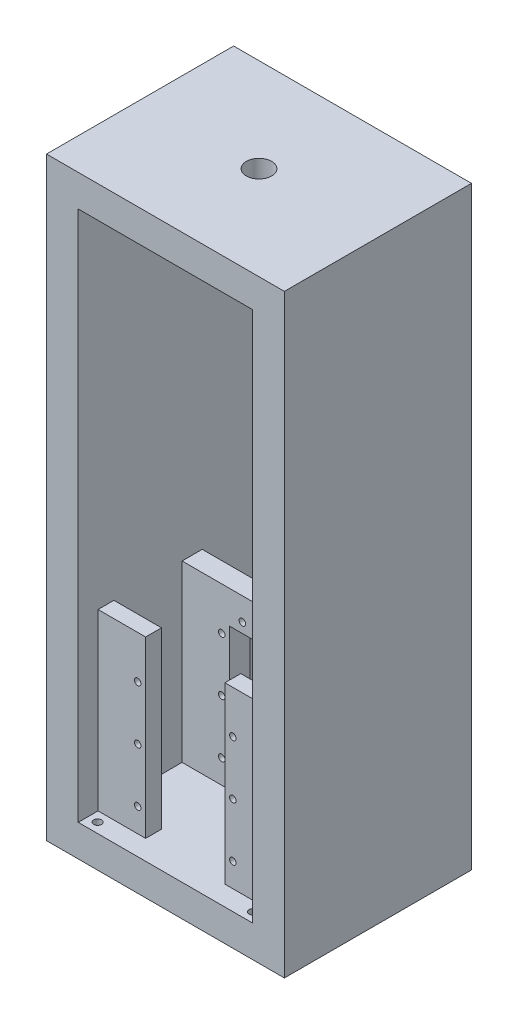
SolidWorks part; units mm, degrees
ref_plane "Front Plane" through (0, 0, 0) normal (0, 0, 1) x (1, 0, 0)
ref_plane "Top Plane" through (0, 0, 0) normal (0, 1, 0) x (1, 0, 0)
ref_plane "Right Plane" through (0, 0, 0) normal (1, 0, 0) x (0, 0, -1)
sketch "Sketch1" plane through (0, 0, 0) normal (0, 0, 1) x (1, 0, 0)
  line L1 (0, 0) -> (75, 0)
  line L2 (0, 0) -> (0, 187.5)
  line L3 (0, 187.5) -> (75, 187.5)
  line L4 (75, 0) -> (75, 187.5)
  line L5 (10, 10) -> (65, 10)
  line L6 (10, 10) -> (10, 177.5)
  line L7 (10, 177.5) -> (65, 177.5)
  line L8 (65, 10) -> (65, 177.5)
  dimension "D1" = 75
  dimension "D2" = 187.5
  dimension "D3" = 10
  dimension "D4" = 10
  dimension "D5" = 10
  dimension "D6" = 10
extrude "Boss-Extrude1" add sketch "Sketch1" against normal blind 59
ref_plane "Plane1" through (0, 0, -37.5) normal (0, 0, 1) x (1, 0, 0)
hole_wizard "Tap Drill for M5x0.8 Tap2" positions "Sketch8" profile "Sketch9" hole size "M5x0.8" standard "ANSI Metric" end condition through all
sketch "Sketch8" plane through (0, 10, 0) normal (0, 1, 0) x (1, 0, 0)
  line L0 (37.5, 59) -> (37.5, 0) construction
  line L1 (10, 59) -> (65, 59) construction
  line L2 (10, 0) -> (65, 0) construction
  point P0 (37.5, 29.5)
sketch "Sketch9" plane through (37.5, 10, -29.5) normal (1, 0, 0) x (0, 0, 1)
  line L0 (0, 0) -> (0, 10)
  line L1 (0, 10) -> (2.1, 10)
  line L2 (2.1, 10) -> (2.1, 0)
  line L5 (2.1, 0) -> (0, 0)
  line L11 (0, -6.35) -> (0, 107.95) construction
  dimension "Thru Hole Dia." = 4.2
  dimension "Thru Hole Depth" = 10
sketch "Sketch13" plane through (0, 10, 0) normal (0, 1, 0) x (1, 0, 0)
  line L0 (65, 59) -> (65, 0) construction
  line L1 (65, 32.75) -> (50, 32.75)
  line L2 (65, 32.75) -> (65, 39.1)
  line L3 (65, 39.1) -> (50, 39.1)
  line L4 (50, 32.75) -> (50, 39.1)
  line L5 (37.5, 59) -> (37.5, 0) construction
  line L6 (10, 59) -> (65, 59) construction
  line L7 (10, 0) -> (65, 0) construction
  line L8 (10, 39.1) -> (25, 39.1)
  line L9 (25, 32.75) -> (25, 39.1)
  line L10 (10, 32.75) -> (25, 32.75)
  line L11 (10, 32.75) -> (10, 39.1)
  line L12 (10, 11.25) -> (25, 11.25)
  line L13 (65, 6.25) -> (50, 6.25)
  line L14 (65, 6.25) -> (65, 11.25)
  line L15 (65, 11.25) -> (50, 11.25)
  line L16 (50, 6.25) -> (50, 11.25)
  line L17 (25, 6.25) -> (25, 11.25)
  line L18 (10, 6.25) -> (25, 6.25)
  line L19 (10, 6.25) -> (10, 11.25)
  dimension "D1" = 26.25
  dimension "D2" = 12.5
  dimension "D3" = 6.35
  dimension "D4" = 6.25
  dimension "D5" = 5
  dimension "D6" = 15
extrude "Boss-Extrude2" add sketch "Sketch13" along normal blind 55
sketch "Sketch14" plane through (50, 0, 0) normal (-1, 0, 0) x (0, 0, 1)
  line L0 (-32.75, 65) -> (-32.75, 10) construction
  line L1 (-39.1, 65) -> (-32.75, 65)
  line L2 (-39.1, 65) -> (-39.1, 54.7)
  line L3 (-39.1, 54.7) -> (-32.75, 54.7)
  line L4 (-32.75, 65) -> (-32.75, 54.7)
  dimension "D1" = 10.3
extrude "Boss-Extrude3" add sketch "Sketch14" along normal up to surface (25 mm away) contours L1 L4 L3 L2 up to face at (25, 37.5, -35.925)
sketch "Sketch17" plane through (0, 0, -39.1) normal (0, 0, -1) x (-1, 0, 0)
  line L0 (-37.5, 65) -> (-37.5, 10) construction
  line L1 (-65, 65) -> (-10, 65) construction
  line L2 (-10, 10) -> (-65, 10) construction
  line L3 (-22.5, 65) -> (-22.5, 10) construction
  line L5 (-25, 10) -> (-10, 10) construction
  line L6 (-29, 65) -> (-29, 10) construction
  line L8 (-65, 17.5) -> (-10, 17.5) construction
  line L9 (-65, 10) -> (-65, 177.5) construction
  line L10 (-10, 65) -> (-10, 10) construction
  line L11 (-65, 34.5) -> (-10, 34.5) construction
  line L12 (-65, 51.5) -> (-10, 51.5) construction
  line L13 (-65, 57.8) -> (-10, 57.8) construction
  line L14 (-52.5, 65) -> (-52.5, 10) construction
  line L15 (-46, 65) -> (-46, 10) construction
  dimension "D1" = 15
  dimension "D2" = 6.5
  dimension "D3" = 7.5
  dimension "D4" = 17
  dimension "D5" = 17
  dimension "D6" = 6.3
hole_wizard "Tap Drill for M2.5x0.45 Tap1" positions "Sketch18" profile "Sketch19" hole size "M2.5x0.45" standard "ANSI Metric" end condition through all
sketch "Sketch18" plane through (0, 0, -39.1) normal (0, 0, -1) x (-1, 0, 0)
  line L0 (-65, 57.8) -> (-10, 57.8) construction
  line L1 (-46, 65) -> (-46, 10) construction
  line L2 (-29, 65) -> (-29, 10) construction
  line L3 (-22.5, 65) -> (-22.5, 10) construction
  line L4 (-65, 51.5) -> (-10, 51.5) construction
  line L5 (-52.5, 65) -> (-52.5, 10) construction
  line L6 (-65, 34.5) -> (-10, 34.5) construction
  line L7 (-65, 17.5) -> (-10, 17.5) construction
  point P0 (-46, 57.8)
  point P2 (-52.5, 51.5)
  point P4 (-52.5, 34.5)
  point P6 (-52.5, 17.5)
  point P8 (-22.5, 17.5)
  point P10 (-22.5, 34.5)
  point P12 (-22.5, 51.5)
  point P14 (-29, 57.8)
sketch "Sketch19" plane through (46, 57.8, -39.1) normal (1, 0, 0) x (0, 1, 0)
  line L0 (0, 0) -> (0, 39.1)
  line L1 (0, 39.1) -> (1.025, 39.1)
  line L2 (1.025, 39.1) -> (1.025, 0)
  line L5 (1.025, 0) -> (0, 0)
  line L11 (0, -6.35) -> (0, 107.95) construction
  dimension "Thru Hole Dia." = 2.05
  dimension "Thru Hole Depth" = 39.1
hole_wizard "Tap Drill for M3x0.5 Tap1" positions "Sketch20" profile "Sketch21" hole size "M3x0.5" standard "ANSI Metric" end condition through all
sketch "Sketch20" plane through (0, 10, 0) normal (0, 1, 0) x (1, 0, 0)
  line L0 (10, 3.125) -> (65, 3.125) construction
  line L1 (10, 6.25) -> (10, 0) construction
  line L2 (65, 6.25) -> (65, 0) construction
  line L4 (13, 6.25) -> (13, 0) construction
  line L5 (10, 6.25) -> (25, 6.25) construction
  line L6 (10, 0) -> (65, 0) construction
  line L8 (62, 6.25) -> (62, 0) construction
  line L9 (50, 6.25) -> (65, 6.25) construction
  line L11 (65, 53) -> (10, 53)
  line L12 (65, 59) -> (65, 39.1) construction
  line L13 (10, 59) -> (10, 39.1) construction
  line L15 (10, 59) -> (65, 59) construction
  line L16 (60, 53) -> (60, 59) construction
  line L18 (15, 53) -> (15, 59) construction
  point P0 (13, 3.125)
  point P2 (62, 3.125)
  point P37 (60, 53)
  point P39 (15, 53)
  dimension "D1" = 3
  dimension "D2" = 3
  dimension "D3" = 6
  dimension "D4" = 5
  dimension "D5" = 5
sketch "Sketch21" plane through (13, 10, -3.125) normal (1, 0, 0) x (0, 0, 1)
  line L0 (0, 0) -> (0, 10)
  line L1 (0, 10) -> (1.25, 10)
  line L2 (1.25, 10) -> (1.25, 0)
  line L5 (1.25, 0) -> (0, 0)
  line L11 (0, -6.35) -> (0, 107.95) construction
  dimension "Thru Hole Dia." = 2.5
  dimension "Thru Hole Depth" = 10
sketch "Sketch22" plane through (0, 187.5, 0) normal (0, 1, 0) x (1, 0, 0)
  line L0 (37.5, 59) -> (37.5, 0) construction
  line L1 (75, 59) -> (0, 59) construction
  line L2 (75, 0) -> (0, 0) construction
  line L3 (75, 29.5) -> (0, 29.5) construction
  line L4 (75, 59) -> (75, 0) construction
  line L5 (0, 59) -> (0, 0) construction
  circle A0 centre (37.5, 29.5) radius 4
  dimension "D1" = 8
extrude "Cut-Extrude1" cut sketch "Sketch22" against normal up to next
